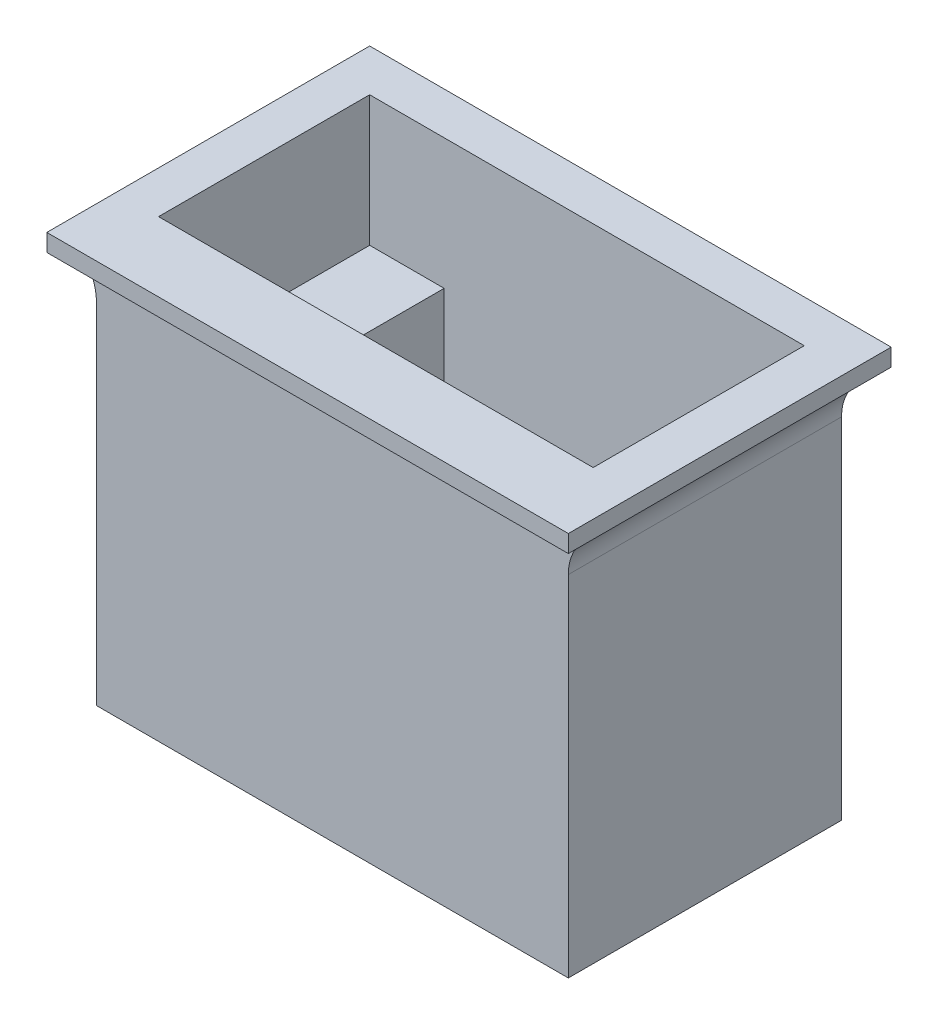
SolidWorks part; units mm, degrees
ref_plane "Front Plane" through (0, 0, 0) normal (0, 0, 1) x (1, 0, 0)
ref_plane "Top Plane" through (0, 0, 0) normal (0, 1, 0) x (1, 0, 0)
ref_plane "Right Plane" through (0, 0, 0) normal (1, 0, 0) x (0, 0, -1)
sketch "Sketch1" plane through (0, 0, 0) normal (0, 1, 0) x (1, 0, 0)
  line L0 (8.6, 5.9429) -> (8.6, -20.9814) construction
  line L1 (-10.4, 5.9429) -> (27.6, 5.9429)
  line L2 (-10.4, 5.9429) -> (-10.4, -16.0571)
  line L3 (-10.4, -16.0571) -> (27.6, -16.0571)
  line L4 (27.6, 5.9429) -> (27.6, -16.0571)
  dimension "D1" = 38
  dimension "D2" = 22
extrude "Boss-Extrude1" add sketch "Sketch1" along normal blind 33
sketch "Sketch2" plane through (0, 33, 0) normal (0, 1, 0) x (1, 0, 0)
  line L0 (27.6, 5.9429) -> (-10.4, 5.9429) construction
  line L1 (-9, 4.5429) -> (26, 4.5429)
  line L2 (-9, 4.5429) -> (-9, -12.4571)
  line L3 (-9, -12.4571) -> (26, -12.4571)
  line L4 (26, 4.5429) -> (26, -12.4571)
  line L5 (-10.4, 5.9429) -> (-10.4, -16.0571) construction
  dimension "D1" = 35
  dimension "D2" = 17
  dimension "D3" = 1.4
  dimension "D4" = 1.4
extrude "Cut-Extrude1" cut sketch "Sketch2" against normal blind 28
sketch "Sketch3" plane through (0, 5, 0) normal (0, 1, 0) x (1, 0, 0)
  line L0 (-9, -12.4571) -> (26, -12.4571) construction
  line L1 (-9, 4.5429) -> (-3, 4.5429)
  line L2 (-9, 4.5429) -> (-9, -12.4571)
  line L3 (-9, -12.4571) -> (-3, -12.4571)
  line L4 (-3, 4.5429) -> (-3, -12.4571)
  line L5 (26, 4.5429) -> (-9, 4.5429) construction
  line L6 (20, 4.5429) -> (26, 4.5429)
  line L7 (20, 4.5429) -> (20, -12.4571)
  line L8 (20, -12.4571) -> (26, -12.4571)
  line L9 (26, 4.5429) -> (26, -12.4571)
  dimension "D1" = 6
  dimension "D2" = 6
extrude "Boss-Extrude2" add sketch "Sketch3" along normal blind 17.5
sketch "Sketch4" plane through (0, 33, 0) normal (0, 1, 0) x (1, 0, 0)
  line L1 (-10.4, 5.9429) -> (27.6, 5.9429)
  line L2 (-10.4, 5.9429) -> (-10.4, -16.0571)
  line L3 (-10.4, -16.0571) -> (27.6, -16.0571)
  line L4 (27.6, 5.9429) -> (27.6, -16.0571)
extrude "Extrude-Thin2" add sketch "Sketch4" against normal blind 1.4 thin thin type one direction wall 2
sketch "Sketch5" plane through (0, 22.5, 0) normal (0, 1, 0) x (1, 0, 0)
  line L0 (-3, -12.4571) -> (-3, 4.5429) construction
  circle A0 centre (-5.5, -3.8921) radius 1
  dimension "D1" = 2
  dimension "D2" = 2.5
extrude "Cut-Extrude2" cut sketch "Sketch5" against normal blind 3
sketch "Sketch6" plane through (0, 22.5, 0) normal (0, 1, 0) x (1, 0, 0)
  circle A0 centre (22.9531, -4.1157) radius 1
  dimension "D1" = 2
extrude "Cut-Extrude3" cut sketch "Sketch6" against normal blind 3
sketch "Sketch7" plane through (-3, 0, 0) normal (1, 0, 0) x (0, 0, -1)
  line L0 (5.9429, 31.6) -> (5.9429, 0) construction
  line L1 (0.9429, 4.0414) -> (-8.4571, 4.0414)
  line L2 (0.9429, 4.0414) -> (0.9429, 8.5414)
  line L3 (0.9429, 8.5414) -> (-8.4571, 8.5414)
  line L4 (-8.4571, 4.0414) -> (-8.4571, 8.5414)
  point P4 (0.9429, 6.2914)
  dimension "D1" = 9.4
  dimension "D2" = 4.5
  dimension "D3" = 5
extrude "Cut-Extrude4" cut sketch "Sketch7" against normal blind 10
sketch "Sketch8" plane through (0, 5, 0) normal (0, 1, 0) x (1, 0, 0)
  line L1 (-1.4079, -8.7279) -> (18.5921, -8.7279)
  line L2 (-1.4079, -8.7279) -> (-1.4079, 1.2721)
  line L3 (-1.4079, 1.2721) -> (18.5921, 1.2721)
  line L4 (18.5921, -8.7279) -> (18.5921, 1.2721)
  dimension "D1" = 10
  dimension "D2" = 20
extrude "Cut-Extrude5" cut sketch "Sketch8" against normal blind 1.5
sketch "Sketch9" plane through (0, 3.5, 0) normal (0, 1, 0) x (1, 0, 0)
  circle A0 centre (8.8083, -3.6349) radius 3.7
  circle A3 centre (1.6083, -3.6349) radius 1
  circle A4 centre (16.0083, -3.6349) radius 1
  dimension "D1" = 7.4
  dimension "D2" = 3.5
  dimension "D5" = 2
  dimension "D4" = 2
  dimension "D3" = 3.5
extrude "Cut-Extrude6" cut sketch "Sketch9" against normal blind 1.7
fillet "Fillet1" radius 4 4 edges at (18.5921, 4.25, -1.2721) (18.5921, 4.25, 8.7279) (-1.4079, 4.25, -1.2721) (-1.4079, 4.25, 8.7279)
fillet "Fillet2" radius 3 1 edges at (-3, 8.5414, 3.7571)
fillet "Fillet3" radius 4 2 edges at (-10.4, 31.6, 5.0571) (27.6, 31.6, 5.0571)
